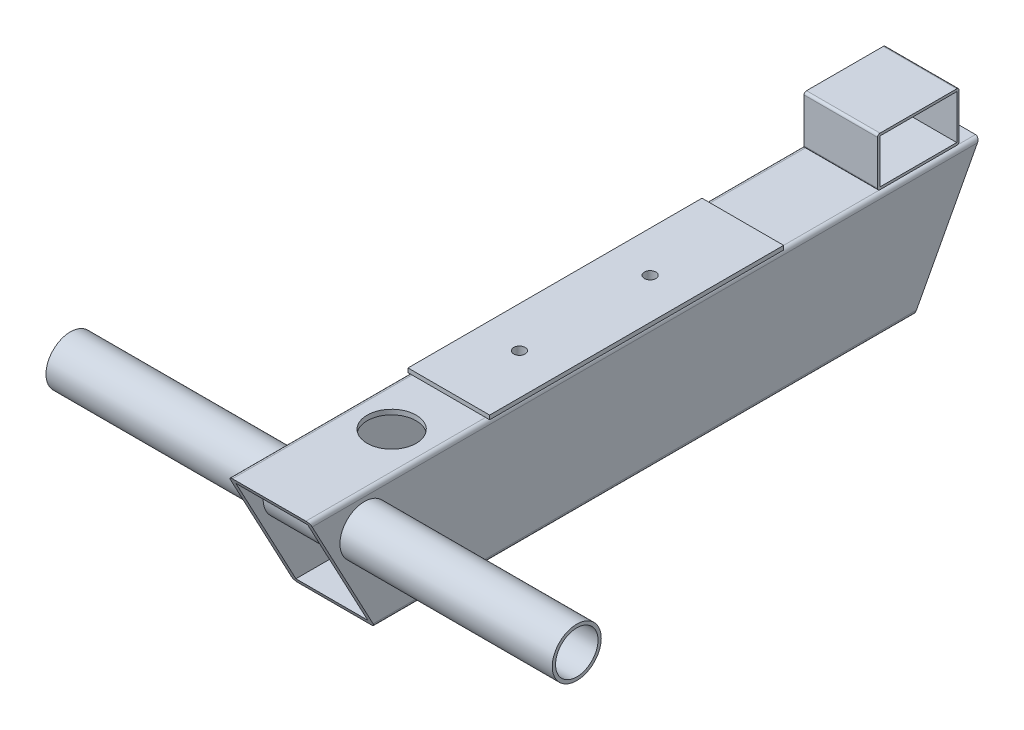
SolidWorks part; units mm, degrees
material "Structural Steel"
ref_plane "Piano frontale" through (0, 0, 0) normal (0, 0, 1) x (1, 0, 0)
ref_plane "Piano superiore" through (0, 0, 0) normal (0, 1, 0) x (1, 0, 0)
ref_plane "Piano destro" through (0, 0, 0) normal (1, 0, 0) x (0, 0, -1)
sketch "Schizzo1" plane through (0, 0, 0) normal (0, 0, 1) x (1, 0, 0)
  line L1 (5, 0) -> (95, 0)
  line L2 (0, 5) -> (0, 145)
  line L3 (5, 150) -> (95, 150)
  line L4 (100, 5) -> (100, 145)
  arc A0 (0, 145) -> (5, 150) centre (5, 145) cw
  arc A1 (95, 150) -> (100, 145) centre (95, 145) cw
  arc A2 (95, 0) -> (100, 5) centre (95, 5) ccw
  arc A3 (5, 0) -> (0, 5) centre (5, 5) cw
  point P7 (0, 150)
  point P12 (100, 0)
  point P15 (0, 0)
  dimension "D3" = 5
  dimension "D1" = 100
  dimension "D2" = 150
extrude "Estrusione-Sottile1" add sketch "Schizzo1" along normal blind 1000 thin thin type one direction reverse wall 6
sketch "Schizzo2" plane through (100, 0, 0) normal (1, 0, 0) x (0, 0, -1)
  line L0 (-920, 178.0473) -> (-920, -33.1937) construction
  line L1 (-1000, 5) -> (-1000, 145) construction
  line L2 (-920, 0) -> (-1000, 150)
  line L3 (-1000, 150) -> (-1000, 0)
  line L4 (-1000, 0) -> (-920, 0)
  dimension "D1" = 80
extrude "Estrusione1" cut sketch "Schizzo2" against normal through all
sketch "Schizzo3" plane through (100, 0, 0) normal (1, 0, 0) x (0, 0, -1)
  line L0 (-260, 227.1862) -> (-260, -99.833) construction
  line L1 (-180, 227.1862) -> (-180, -97.5683) construction
  line L2 (-180, 150) -> (-260, 0)
  line L4 (-260, 0) -> (0, 0)
  line L5 (0, 0) -> (0, 150)
  line L6 (-1000, 150) -> (0, 150) construction
  line L7 (-180, 150) -> (0, 150)
  dimension "D1" = 660
  dimension "D2" = 80
extrude "Estrusione2" cut sketch "Schizzo3" against normal through all
sketch "Schizzo4" plane through (0, 0, 0) normal (0, -1, 0) x (1, 0, 0)
  line L0 (50, 920) -> (50, 716.89) construction
  line L1 (5, 920) -> (95, 920) construction
  circle A0 centre (50, 850) radius 30
  dimension "D1" = 60
  dimension "D2" = 70
extrude "Estrusione3" cut sketch "Schizzo4" against normal through all
sketch "Schizzo12" plane through (0, 150, 0) normal (0, 1, 0) x (1, 0, 0)
  line L0 (50, -1850) -> (50, 48150) construction
  circle A0 centre (50, -693.5) radius 7
  circle A1 centre (50, -533.5) radius 7
  circle A2 centre (50, -850) radius 30 construction
  dimension "D1" = 14
  dimension "D2" = 14
  dimension "D3" = 156.5
  dimension "D4" = 160
extrude "Taglio-Estrusione1" cut sketch "Schizzo12" against normal through all
sketch "Schizzo5" plane through (0, 150, 0) normal (0, 1, 0) x (1, 0, 0)
  line L0 (0, -997.3333) -> (0, -182.6667) construction
  line L1 (0, -780) -> (100, -780)
  line L2 (0, -780) -> (0, -420)
  line L3 (0, -420) -> (100, -420)
  line L4 (100, -780) -> (100, -420)
  line L5 (100, -997.3333) -> (100, -182.6667) construction
  circle A0 centre (50, -850) radius 30 construction
  dimension "D1" = 70
  dimension "D2" = 360
extrude "Estrusione4" add sketch "Schizzo5" along normal blind 5
sketch "Schizzo6" plane through (0, 155, 0) normal (0, 1, 0) x (1, 0, 0)
  line L0 (50, -1850) -> (50, 48150) construction
  line L1 (-100.135, -613.5) -> (203.9847, -613.5) construction
  circle A0 centre (50, -850) radius 30 construction
  circle A1 centre (50, -533.5) radius 7
  circle A2 centre (50, -693.5) radius 7
  dimension "D1" = 236.5
  dimension "D2" = 14
  dimension "D3" = 14
  dimension "D4" = 80
  dimension "D5" = 80
extrude "Estrusione5" cut sketch "Schizzo6" against normal through all
sketch "Schizzo9" plane through (100, 0, 0) normal (1, 0, 0) x (0, 0, -1)
  line L0 (-1000, 150) -> (-780, 150) construction
  line L1 (-922.6667, 5) -> (-997.3333, 145) construction
  circle A0 centre (-933.3333, 110) radius 30
  dimension "D1" = 60
  dimension "D2" = 40
  dimension "D3" = 40
extrude "Estrusione8" cut sketch "Schizzo9" against normal through all
sketch "Schizzo10" plane through (100, 0, 0) normal (1, 0, 0) x (0, 0, -1)
  circle A0 centre (-933.3333, 110) radius 30
extrude "Estrusione-Sottile2" add sketch "Schizzo10" along normal blind 260 and the other way blind 360 thin thin type one direction reverse wall 4
sketch "Schizzo11" plane through (100, 0, 0) normal (1, 0, 0) x (0, 0, -1)
  line L0 (-420, 150) -> (-180, 150) construction
  line L1 (-203, 150) -> (-297, 150)
  line L2 (-200, 153) -> (-200, 207)
  line L3 (-203, 210) -> (-297, 210)
  line L4 (-300, 153) -> (-300, 207)
  arc A0 (-203, 150) -> (-200, 153) centre (-203, 153) ccw
  arc A1 (-200, 207) -> (-203, 210) centre (-203, 207) ccw
  arc A2 (-297, 150) -> (-300, 153) centre (-297, 153) cw
  arc A3 (-297, 210) -> (-300, 207) centre (-297, 207) ccw
  point P9 (-200, 150)
  point P12 (-200, 210)
  point P15 (-300, 150)
  point P18 (-300, 210)
  dimension "D4" = 3
  dimension "D1" = 100
  dimension "D2" = 60
  dimension "D3" = 20
extrude "Estrusione-Sottile3" add sketch "Schizzo11" against normal blind 90 from offset 5 thin offset against normal yes thin type one direction reverse wall 3
ref_axis "Assi1" through (-260, 110, 933.3333) along (1, 0, 0)
ref_plane "Piano1" through (50, 0, 0) normal (-1, 0, 0) x (0, 0, 1)
